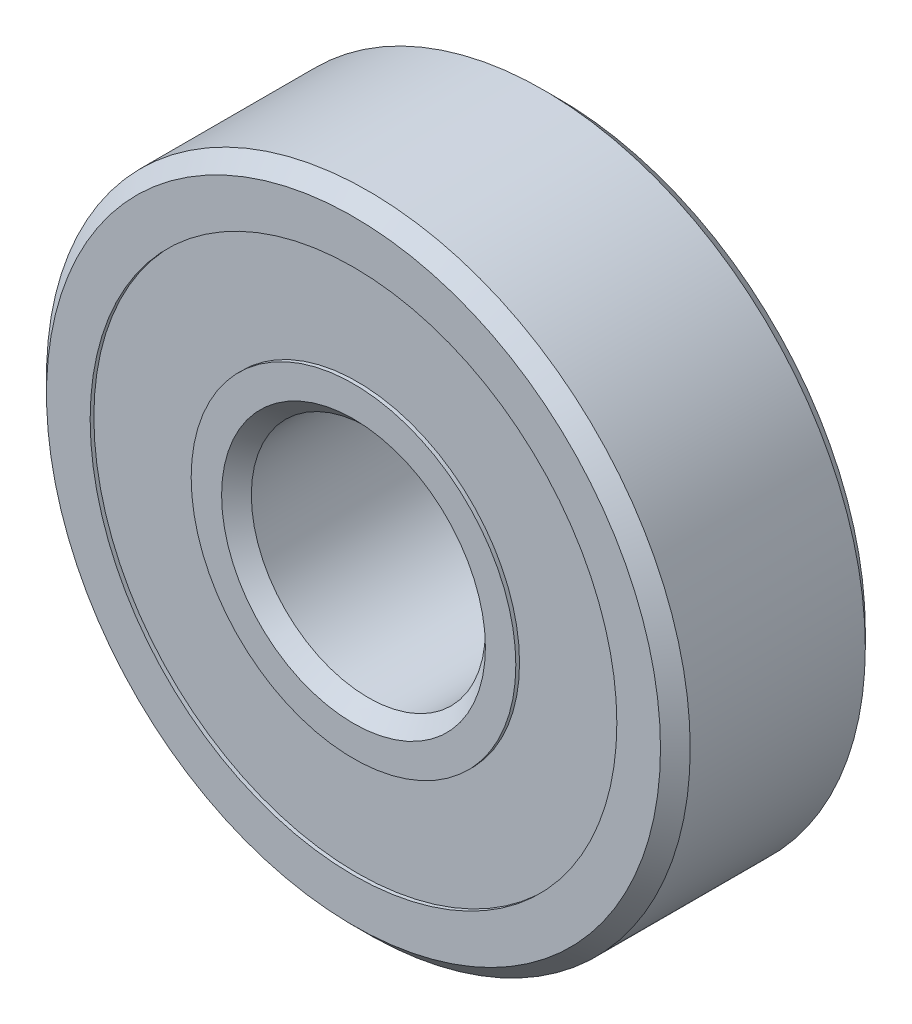
SolidWorks part; units mm, degrees
ref_plane "Front Plane" through (0, 0, 0) normal (0, 0, 1) x (1, 0, 0)
ref_plane "Top Plane" through (0, 0, 0) normal (0, 1, 0) x (1, 0, 0)
ref_plane "Right Plane" through (0, 0, 0) normal (1, 0, 0) x (0, 0, -1)
sketch "Sketch1" plane through (0, 0, 0) normal (0, 0, 1) x (1, 0, 0)
  circle A0 centre (0, 0) radius 11
  circle A1 centre (0, 0) radius 4
  dimension "D1" = 8
  dimension "D2" = 22
extrude "Boss-Extrude1" add sketch "Sketch1" along normal blind 7
chamfer "Chamfer1" distance 0.508 angle 45 3 edges at (11, 0, 0) (4, 0, 7) (11, 0, 7)
sketch "Sketch2" plane through (0, 0, 0) normal (0, 0, -1) x (-1, 0, 0)
  circle A0 centre (0, 0) radius 5.5476
  circle A1 centre (0, 0) radius 9.0001
extrude "Cut-Extrude1" cut sketch "Sketch2" against normal blind 0.127
ref_plane "Plane1" through (0, 0, 3.5) normal (0, 0, -1) x (-1, 0, 0)
mirror "Mirror1" about plane through (0, 0, 3.5) normal (0, 0, -1) of "Cut-Extrude1"
